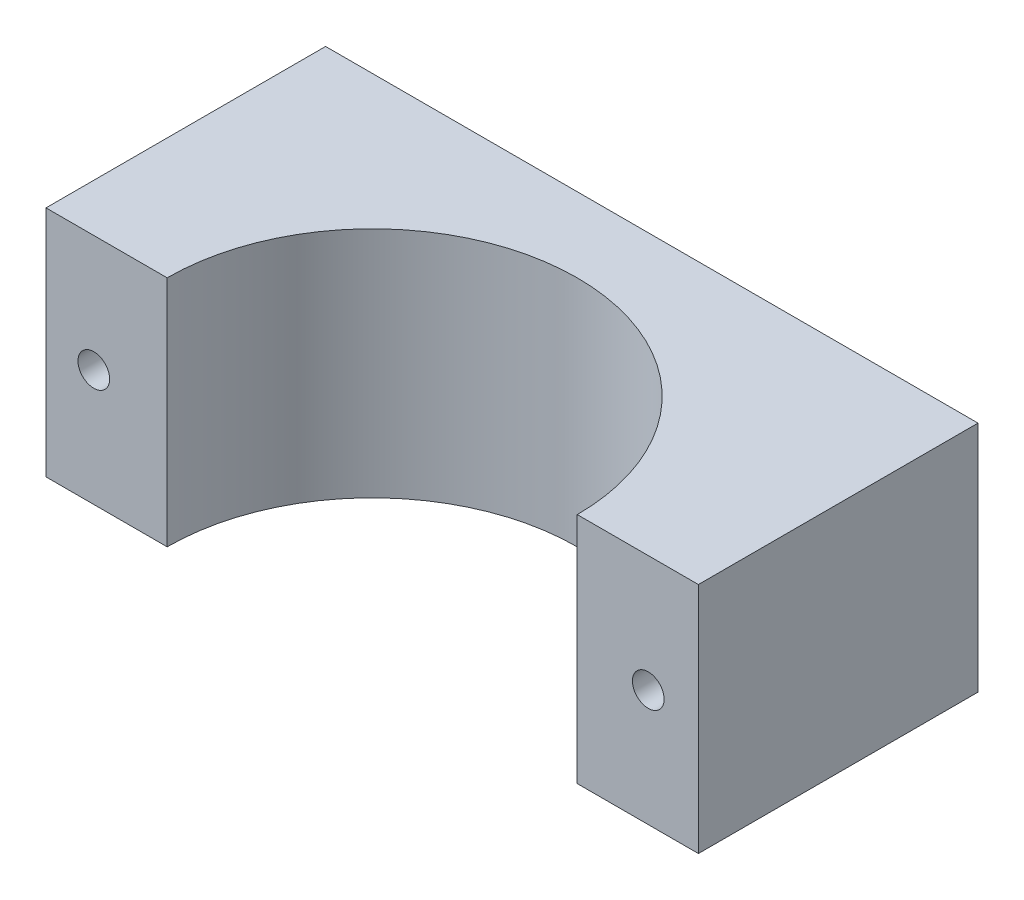
SolidWorks part; units mm, degrees
ref_plane "Front Plane" through (0, 0, 0) normal (0, 0, 1) x (1, 0, 0)
ref_plane "Top Plane" through (0, 0, 0) normal (0, 1, 0) x (1, 0, 0)
ref_plane "Right Plane" through (0, 0, 0) normal (1, 0, 0) x (0, 0, -1)
sketch "Sketch1" plane through (0, 0, 0) normal (0, 1, 0) x (1, 0, 0)
  line L0 (-29.5461, 0) -> (40.4539, 0) construction
  line L1 (-29.5461, 0) -> (-16.5461, 0)
  line L2 (40.4539, 0) -> (27.4539, 0)
  line L4 (-29.5461, 0) -> (-29.5461, 30)
  line L5 (-29.5461, 30) -> (40.4539, 30)
  line L6 (40.4539, 30) -> (40.4539, 0)
  arc A1 (27.4539, 0) -> (-16.5461, 0) centre (5.4539, 0) ccw
  dimension "D1" = 70
  dimension "D2" = 13
  dimension "D5" = 30
extrude "Boss-Extrude1" add sketch "Sketch1" along normal blind 25 contours A1 L2 L6 L5 L4 L1 region at (-28.7845, 0, -15)
sketch "Sketch3" plane through (0, 0, -30) normal (0, 0, -1) x (-1, 0, 0)
  line L0 (-40.4539, 12.5) -> (29.5461, 12.5) construction
  line L1 (-40.4539, 25) -> (-40.4539, 0) construction
  line L2 (29.5461, 25) -> (29.5461, 0) construction
  line L3 (-35.0739, 25) -> (-35.0739, 0) construction
  line L4 (29.5461, 25) -> (-40.4539, 25) construction
  line L5 (29.5461, 0) -> (-40.4539, 0) construction
  line L6 (24.4161, 25) -> (24.4161, 0) construction
  circle A0 centre (-35.0739, 12.5) radius 1.7
  circle A1 centre (24.4161, 12.5) radius 1.7
  dimension "D1" = 5.38
  dimension "D2" = 5.13
extrude "Boss-Extrude2" add sketch "Sketch3" against normal blind 30
extrude "Cut-Extrude1" cut sketch "Sketch3<2>" against normal blind 30
sketch "Sketch3<2>" plane through (0, 0, -30) normal (0, 0, -1) x (-1, 0, 0) same geometry as "Sketch3"
